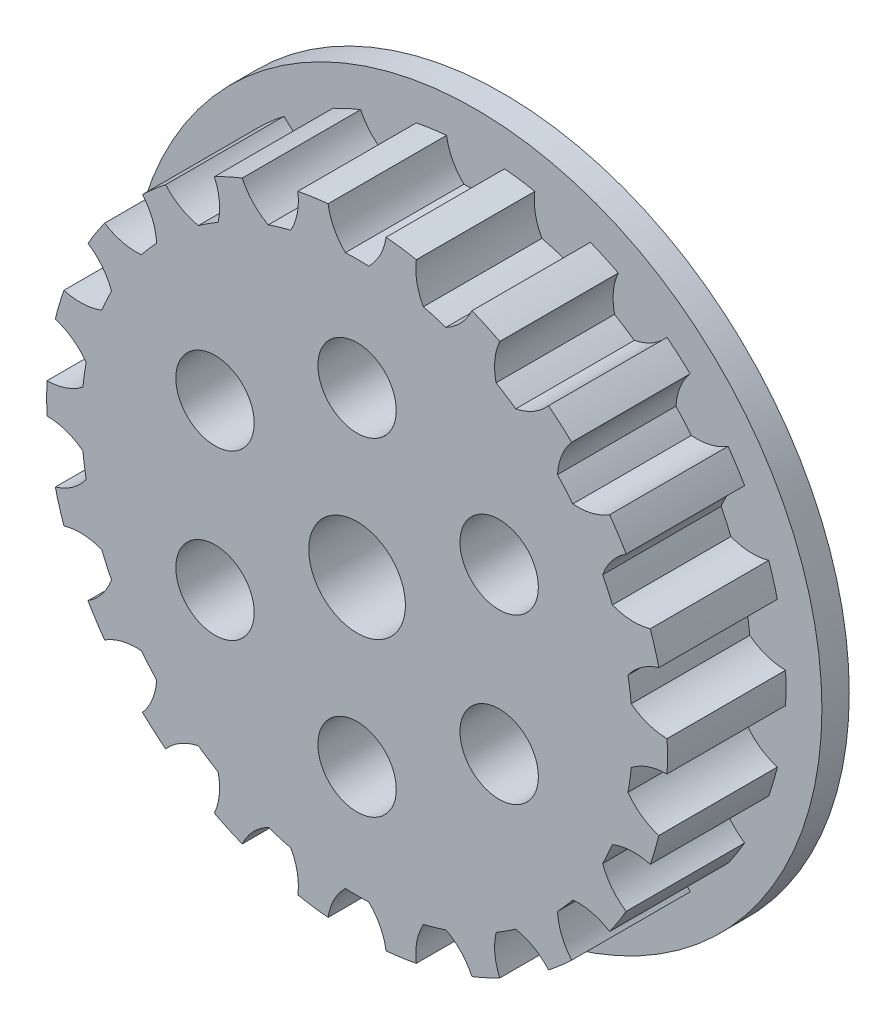
SolidWorks part; units mm, degrees
note: The reader was unsure of these and kept them because the rebuilt part matched: shared geometry of "ｽｹｯﾁ1<6>", "ｽｹｯﾁ1<7>".
material "3.1325 (EN-AW 2017A)"
ref_plane "正面" through (0, 0, 0) normal (0, 0, 1) x (1, 0, 0)
ref_plane "平面" through (0, 0, 0) normal (0, 1, 0) x (1, 0, 0)
ref_plane "右側面" through (0, 0, 0) normal (1, 0, 0) x (0, 0, -1)
sketch "ｽｹｯﾁ1" plane through (0, 0, 0) normal (0, 0, 1) x (1, 0, 0)
  circle A0 centre (0, 0) radius 17.507 construction
  circle A1 centre (0, 0) radius 17.027
  circle A176 centre (0, 0) radius 19
  circle A177 centre (0, 0) radius 9 construction
  point P17 (0, 0)
  point P44 (0, 0)
  point P271 (0, 9)
  point P361 (0, 0)
  dimension "D1" = 38
  dimension "D2" = 18
  dimension "D4" = 35.0141
  dimension "D5" = 0.48
extrude "ﾎﾞｽ - 押し出し1" add sketch "ｽｹｯﾁ1" along normal blind 6 contours A1
extrude "ﾎﾞｽ - 押し出し2" add sketch "ｽｹｯﾁ1<6>" along normal blind 8 contours A1
sketch "ｽｹｯﾁ1<6>" plane through (0, 0, 0) normal (0, 0, 1) x (1, 0, 0) same geometry as "ｽｹｯﾁ1"
extrude "ﾎﾞｽ - 押し出し3" add sketch "ｽｹｯﾁ1<7>" along normal blind 1.5 contours A176
sketch "ｽｹｯﾁ1<7>" plane through (0, 0, 0) normal (0, 0, 1) x (1, 0, 0) same geometry as "ｽｹｯﾁ1"
sketch "ｽｹｯﾁ3" plane through (0, 0, 0) normal (0, 0, 1) x (1, 0, 0)
  line L0 (0, 14.0083) -> (0, 21.7977) construction
  arc A0 (1.5895, 16.9527) -> (-1.5895, 16.9527) centre (0, 0) ccw
  circle A1 centre (0, 0) radius 17.027 construction
  arc A2 (1.5895, 16.9527) -> (-1.5895, 16.9527) centre (0, 0) ccw
  arc A3 (0.6427, 15.1034) -> (-0.6427, 15.1034) centre (0, 0) ccw
  arc A5 (-0.6427, 15.1034) -> (-1.625, 17.4315) centre (1.625, 17.4315) cw construction
  circle A6 centre (0, 0) radius 17.507 construction
  arc A7 (-0.6427, 15.1034) -> (-1.5895, 16.9527) centre (1.625, 17.4315) cw
  arc A8 (0.6427, 15.1034) -> (1.5895, 16.9527) centre (-1.625, 17.4315) ccw
  dimension "D2" = 3.25
  dimension "D3" = 3.25
  dimension "D1" = 1.91
extrude "ｶｯﾄ - 押し出し3" cut sketch "ｽｹｯﾁ3" along normal through all from offset 1.5 contours A3 A8 A0 A7
pattern_circular "円形ﾊﾟﾀｰﾝ1" count 22 over 360 about axis through (0, 0, 0) along (0, 0, 1) of "ｶｯﾄ - 押し出し3"
hole_wizard "M4 すきま穴2" [suppressed] positions "3Dｽｹｯﾁ1" profile "ｽｹｯﾁ4" hole size "M4" standard "JIS"
sketch3d "3Dｽｹｯﾁ1"
  point P0 (0, 9, 0)
sketch "ｽｹｯﾁ4" plane through (0, 9, 0) normal (1, 0, 0) x (0, 1, 0)
  line L0 (0, 0) -> (0, 6)
  line L1 (0, 6) -> (2.15, 6)
  line L2 (2.15, 6) -> (2.15, 0)
  line L5 (2.15, 0) -> (0, 0)
  line L11 (0, -6.35) -> (0, 107.95) construction
  dimension "通し穴の直径" = 4.3
  dimension "通し穴の深さ" = 6
pattern_circular "円形ﾊﾟﾀｰﾝ3" [suppressed] count 6 over 360
hole_wizard "M4 すきま穴1" positions "3Dｽｹｯﾁ2" profile "ｽｹｯﾁ5" hole size "M4" standard "JIS" end condition through all
sketch3d "3Dｽｹｯﾁ2"
  point P0 (0, 9, 8)
sketch "ｽｹｯﾁ5" plane through (0, 9, 8) normal (1, 0, 0) x (0, -1, 0)
  line L0 (0, 0) -> (0, 8)
  line L1 (0, 8) -> (2.15, 8)
  line L2 (2.15, 8) -> (2.15, 0)
  line L5 (2.15, 0) -> (0, 0)
  line L11 (0, -6.35) -> (0, 107.95) construction
  dimension "通し穴の直径" = 4.3
  dimension "通し穴の深さ" = 8
pattern_circular "円形ﾊﾟﾀｰﾝ2" count 6 over 360 about axis through (0, 0, 0) along (0, 0, 1) of "M4 すきま穴1"
hole_wizard "M5 すきま穴2" [suppressed] positions "3Dｽｹｯﾁ3" profile "ｽｹｯﾁ6" hole size "M5" standard "JIS"
sketch3d "3Dｽｹｯﾁ3"
  point P0 (0, 0, 0)
sketch "ｽｹｯﾁ6" plane through (0, 0, 0) normal (1, 0, 0) x (0, 1, 0)
  line L0 (0, 0) -> (0, 8)
  line L1 (0, 8) -> (2.65, 8)
  line L2 (2.65, 8) -> (2.65, 2.55)
  line L3 (2.65, 2.55) -> (5.2, 0)
  line L5 (5.2, 0) -> (0, 0)
  line L6 (-2.65, 2.55) -> (-5.2, 0) construction
  line L11 (0, -6.35) -> (0, 107.95) construction
  dimension "通し穴の直径" = 5.3
  dimension "通し穴の深さ" = 8
  dimension "表面の皿穴の直径" = 10.4
  dimension "表面の皿穴の角度" = 90
hole_wizard "M5 すきま穴1" positions "3Dｽｹｯﾁ4" profile "ｽｹｯﾁ7" hole size "M5" standard "JIS" end condition through all
sketch3d "3Dｽｹｯﾁ4"
  point P0 (0, 0, 0)
sketch "ｽｹｯﾁ7" plane through (0, 0, 0) normal (1, 0, 0) x (0, 1, 0)
  line L0 (0, 0) -> (0, 8)
  line L1 (0, 8) -> (2.65, 8)
  line L2 (2.65, 8) -> (2.65, 0)
  line L5 (2.65, 0) -> (0, 0)
  line L11 (0, -6.35) -> (0, 107.95) construction
  dimension "通し穴の直径" = 5.3
  dimension "通し穴の深さ" = 8
equation "\"D5@ｽｹｯﾁ1\"=\"フリッパ駆動PLD\""
equation "\"D4@ｽｹｯﾁ1\"=\"フリッパ駆動プーリピッチ円直径_駆動側\""
equation "\"D1@ｽｹｯﾁ3\"=\"フリッパ駆動歯たけ\""
equation "\"ミル径\"= 1"
equation "\"フリッパ駆動ユニットプーリピン位置径\" = 18"
equation "\"フリッパ駆動ピッチ\"= 5"
equation "\"フリッパ駆動ベルト幅\"= 0.75in"
equation "\"フリッパ駆動PLD\"= 0.480"
equation "\"フリッパ駆動歯たけ\"= \"1.91\""
equation "\"フリッパ駆動ベルトピッチ長\"= 390"
equation "\"フリッパ駆動プーリ歯数_駆動側\"= 22"
equation "\"フリッパ駆動プーリ歯数_従動側\"= 44"
equation "\"フリッパ駆動プーリピッチ円直径_駆動側\"= \"フリッパ駆動ピッチ\" * \"フリッパ駆動プーリ歯数_駆動側\" / pi"
equation "\"フリッパ駆動プーリピッチ円直径_従動側\"= \"フリッパ駆動ピッチ\" * \"フリッパ駆動プーリ歯数_従動側\" / pi"
equation "\"フリッパ駆動歯先円直径_駆動側\"= \"フリッパ駆動プーリピッチ円直径_駆動側\" - 2 * \"フリッパ駆動PLD\""
equation "\"フリッパ駆動歯先円直径_従動側\"= \"フリッパ駆動プーリピッチ円直径_従動側\" - 2 * \"フリッパ駆動PLD\""
equation "\"D2@ｽｹｯﾁ1\"=\"フリッパ駆動ユニットプーリピン位置径\""
equation "\"フリッパ駆動ユニットプーリピン数\" = 6"
equation "\"D1@円形ﾊﾟﾀｰﾝ2\"=\"フリッパ駆動ユニットプーリピン数\""
equation "\"D1@円形ﾊﾟﾀｰﾝ3\"=\"フリッパ駆動ユニットプーリピン数\""
